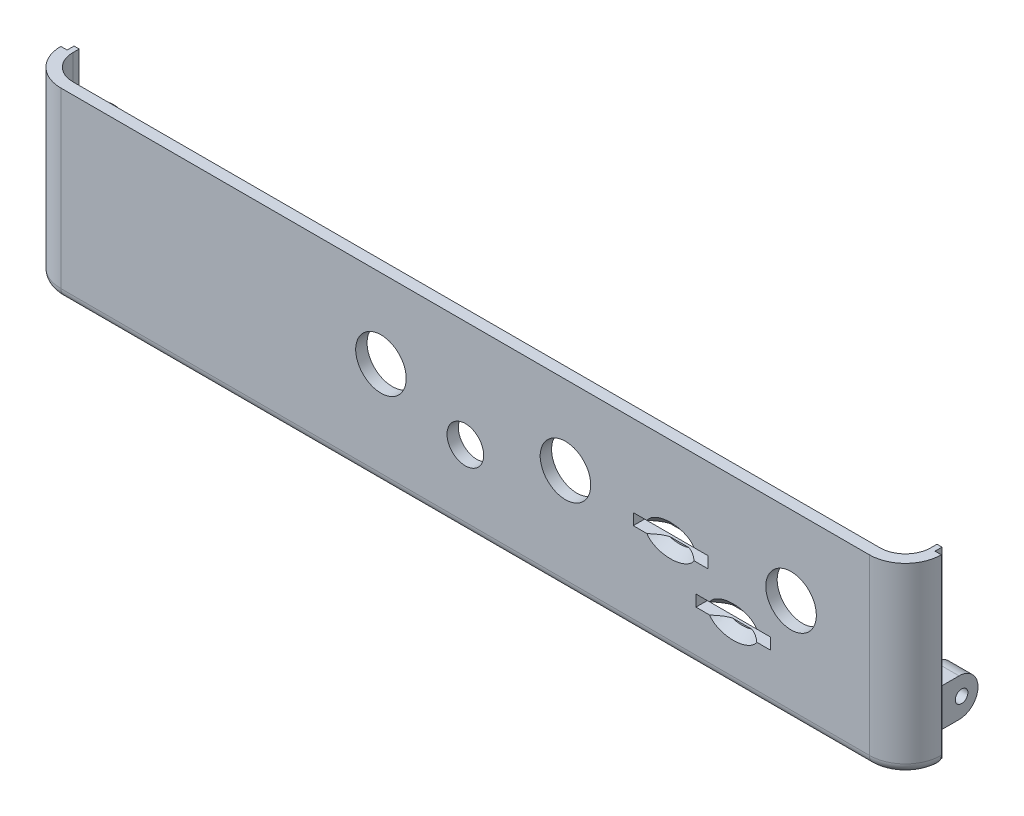
SolidWorks part; units mm, degrees
ref_plane "Спереди" through (0, 0, 0) normal (0, 0, 1) x (1, 0, 0)
ref_plane "Сверху" through (0, 0, 0) normal (0, 1, 0) x (1, 0, 0)
ref_plane "Справа" through (0, 0, 0) normal (1, 0, 0) x (0, 0, -1)
sketch "Эскиз1" plane through (0, 0, 0) normal (0, 0, 1) x (1, 0, 0)
  line L0 (63.5, -15.75) -> (-63.5, -15.75)
  line L1 (63.5, -15.75) -> (67.5, -15.75)
  line L2 (-67.5, -15.75) -> (-63.5, -15.75)
  line L3 (46.9932, -6.75) -> (37.9073, -6.75)
  line L4 (37.9073, -5.75) -> (46.9932, -5.75)
  line L5 (47.9512, -6.625) -> (47.9512, -6.1632)
  line L6 (47.912, -5.875) -> (47.023, -5.875)
  line L7 (47.023, -5.875) -> (47.023, -6.625)
  line L8 (47.023, -6.625) -> (47.9512, -6.625)
  line L9 (36.95, -6.1597) -> (36.95, -6.625)
  line L10 (36.95, -6.625) -> (37.8781, -6.625)
  line L11 (37.8781, -6.625) -> (37.8781, -5.875)
  line L12 (37.8781, -5.875) -> (36.9862, -5.875)
  line L13 (67.5, -13.75) -> (67.5, -15.75)
  line L14 (-67.5, -13.75) -> (-67.5, -15.75)
  line L15 (63.5, -13.75) -> (-63.5, -13.75)
  line L16 (57.5, -7.55) -> (-57.5, -7.55)
  line L17 (-60, -7.55) -> (-60, -9.15)
  line L18 (60, -9.15) -> (60, -7.55)
  line L19 (37.2238, 0.43) -> (27.8238, 0.43)
  line L20 (37.2238, -0.52) -> (27.8238, -0.52)
  line L21 (27.0238, -0.52) -> (27.0238, 0.43)
  line L22 (38.0238, 0.43) -> (38.0238, -0.52)
  line L23 (38.325, 15.75) -> (32.995, 15.75)
  line L24 (43.655, 15.75) -> (38.325, 15.75)
  line L25 (67.5, -13.75) -> (63.5, -13.75)
  line L26 (-63.5, -13.75) -> (-67.5, -13.75)
  line L27 (-26.445, 5.4154) -> (64.8363, 5.4154)
  line L28 (-26.445, 7.0154) -> (64.8363, 7.0154)
  line L29 (63.0185, 5.4154) -> (66.0185, 5.4154)
  line L30 (-24.6275, 7.05) -> (-27.6275, 7.05)
  arc A0 (-11.5687, 1.25) -> (-15.0687, 1.25) centre (-13.3187, 1.25) ccw
  arc A1 (-15.0687, 1.25) -> (-11.5687, 1.25) centre (-13.3187, 1.25) ccw
  arc A2 (53.36, 1.25) -> (49.86, 1.25) centre (51.61, 1.25) ccw
  arc A3 (49.86, 1.25) -> (53.36, 1.25) centre (51.61, 1.25) ccw
  arc A4 (17.6413, 1.25) -> (14.1413, 1.25) centre (15.8913, 1.25) ccw
  arc A5 (14.1413, 1.25) -> (17.6413, 1.25) centre (15.8913, 1.25) ccw
  arc A6 (-1.428, -0.6365) -> (-1.4312, -5.6346) centre (0.0417, -3.1365) ccw
  arc A7 (1.5146, -5.6346) -> (1.5114, -0.6365) centre (0.0417, -3.1365) ccw
  spline S0 degree 3 poles (47.9512, -6.1632) (47.951, -6.1513) (47.9493, -6.1307) (47.9471, -6.1018) knots 0 0 0 0 0.000128 0.000128 0.000128 0.000128 weights 1 1 1 1
  spline S1 degree 3 poles (47.9471, -6.1018) (47.9414, -6.0263) (47.9296, -5.9508) (47.912, -5.875) knots 0 0 0 0 0.000334 0.000334 0.000334 0.000334 weights 1 1 1 1
  spline S2 degree 3 poles (36.953, -6.1018) (36.9512, -6.1281) (36.95, -6.1474) (36.95, -6.1597) knots 0 0 0 0 0.000115 0.000115 0.000115 0.000115 weights 1 1 1 1
  spline S3 degree 3 poles (36.9862, -5.875) (36.9691, -5.9508) (36.958, -6.0264) (36.953, -6.1018) knots 0 0 0 0 0.000335 0.000335 0.000335 0.000335 weights 1 1 1 1
sketch "Эскиз2" plane through (0, 0, 0) normal (0, 0, 1) x (1, 0, 0)
  line L0 (43.655, 15.75) -> (38.325, 15.75) construction
  line L1 (-69.7, 13.75) -> (69.7, 13.75)
  line L2 (-69.7, 13.75) -> (-69.7, -15.35)
  line L3 (-69.7, -15.35) -> (69.7, -15.35)
  line L4 (69.7, 13.75) -> (69.7, -15.35)
  line L5 (63.5, -15.75) -> (-63.5, -15.75) construction
  line L6 (67.5, -13.75) -> (67.5, -15.75) construction
  line L7 (-67.5, -13.75) -> (-67.5, -15.75) construction
  dimension "D1" = 2
  dimension "D2" = 0.4
  dimension "D3" = 2.2
  dimension "D4" = 2.2
extrude "Бобышка-Вытянуть1" add sketch "Эскиз2" along normal blind 1.8
sketch "Эскиз3" plane through (0, 0, 1.8) normal (0, 0, 1) x (1, 0, 0)
  line L0 (37.2238, 0.43) -> (27.8238, 0.43) construction
  line L1 (26.6238, 0.83) -> (38.4238, 0.83)
  line L2 (26.6238, 0.83) -> (26.6238, -0.92)
  line L3 (26.6238, -0.92) -> (38.4238, -0.92)
  line L4 (38.4238, 0.83) -> (38.4238, -0.92)
  line L5 (36.55, -5.35) -> (48.3512, -5.35)
  line L6 (36.55, -5.35) -> (36.55, -7.15)
  line L7 (36.55, -7.15) -> (48.3512, -7.15)
  line L8 (48.3512, -5.35) -> (48.3512, -7.15)
  line L9 (37.2238, -0.52) -> (27.8238, -0.52) construction
  line L10 (27.0238, -0.52) -> (27.0238, 0.43) construction
  line L11 (38.0238, 0.43) -> (38.0238, -0.52) construction
  line L12 (37.9073, -5.75) -> (46.9932, -5.75) construction
  line L13 (46.9932, -6.75) -> (37.9073, -6.75) construction
  line L14 (47.9512, -6.625) -> (47.9512, -6.1632) construction
  line L15 (36.95, -6.1597) -> (36.95, -6.625) construction
  circle A0 centre (0.0417, -3.1365) radius 2.9
  circle A1 centre (-13.3187, 1.25) radius 4
  circle A2 centre (15.8913, 1.25) radius 4
  circle A3 centre (51.61, 1.25) radius 4
  dimension "D1" = 5.8
  dimension "D2" = 8
  dimension "D3" = 0.4
  dimension "D4" = 0.4
  dimension "D5" = 0.4
  dimension "D6" = 0.4
  dimension "D7" = 0.4
  dimension "D8" = 0.4
  dimension "D9" = 0.4
  dimension "D10" = 0.4
extrude "Вырез-Вытянуть1" cut sketch "Эскиз3" against normal blind 1.8
sketch "Эскиз5" plane through (0, 0, 0) normal (0, 0, -1) x (-1, 0, 0)
  line L0 (69.7, -15.35) -> (-69.7, -15.35) construction
  line L1 (69.7, 13.75) -> (67.9, 13.75)
  line L2 (69.7, 13.75) -> (69.7, -15.35)
  line L3 (69.7, -15.35) -> (67.9, -15.35)
  line L4 (67.9, 13.75) -> (67.9, -15.35)
  line L5 (-63.5, -15.75) -> (63.5, -15.75) construction
  line L6 (-69.7, 13.75) -> (-67.9, 13.75)
  line L7 (-69.7, 13.75) -> (-69.7, -15.75)
  line L8 (-69.7, -15.75) -> (-67.9, -15.75)
  line L9 (-67.9, 13.75) -> (-67.9, -15.75)
  dimension "D1" = 1.8
  dimension "D2" = 1.8
extrude "Бобышка-Вытянуть2" add sketch "Эскиз5" along normal blind 5
fillet "Скругление1" radius 4 2 edges at (-67.9, -0.8, 0) (67.9, -0.8, 0)
fillet "Скругление2" radius 5.7 2 edges at (69.7, -0.8, 1.8) (-69.7, -0.8, 1.8)
sketch "Эскиз9" plane through (0, 0, 1.8) normal (0, 0, 1) x (1, 0, 0)
  line L2 (38.4238, 0.83) -> (26.6238, 0.83) construction
  line L3 (26.6238, 0.855) -> (38.4238, 0.855)
  line L4 (26.6238, 0.855) -> (26.6238, -0.945)
  line L5 (26.6238, -0.945) -> (38.4238, -0.945)
  line L6 (38.4238, 0.855) -> (38.4238, -0.945)
  line L9 (38.4238, -0.92) -> (38.4238, 0.83) construction
  dimension "D1" = 1.8
  dimension "D2" = 0.025
  dimension "D3" = 11.8
extrude "Вырез-Вытянуть3" cut sketch "Эскиз9" against normal blind 1.8
sketch "Эскиз11" plane through (0, 0, 1.8) normal (0, 0, 1) x (1, 0, 0)
  line L0 (38.4238, 0.855) -> (26.6238, 0.855) construction
  line L1 (48.3512, -5.35) -> (36.55, -5.35) construction
  line L2 (38.4238, -0.945) -> (38.4238, 0.855) construction
  line L3 (48.3512, -7.15) -> (48.3512, -5.35) construction
  ellipse E0 centre (32.5238, -0.045) end of major axis (28.5238, -0.045) minor radius 2.5
  ellipse E1 centre (42.4512, -6.25) end of major axis (38.4512, -6.25) minor radius 2.5
  dimension "D1" = 0.9
  dimension "D2" = 0.9
  dimension "D3" = 5
  dimension "D4" = 5.9
  dimension "D5" = 5.9
  dimension "D6" = 8
  dimension "D7" = 8
  dimension "D8" = 5
extrude "Вырез-Вытянуть5" cut sketch "Эскиз11" against normal blind 1.4 draft 44
sketch "Эскиз12" plane through (67.9, 0, 0) normal (-1, 0, 0) x (0, 0, 1)
  line L1 (-5, -15.75) -> (0, -15.75)
  line L2 (-5, -15.75) -> (-5, -15.35)
  line L3 (-5, -15.35) -> (0, -15.35)
  line L4 (0, -15.75) -> (0, -15.35)
extrude "Вырез-Вытянуть6" cut sketch "Эскиз12" against normal blind 11.4
sketch "Эскиз13" plane through (0, 0, 0) normal (0, 0, -1) x (-1, 0, 0)
  line L0 (-57.5, -7.55) -> (57.5, -7.55) construction
  line L1 (-60.7, -4.95) -> (-52.7, -4.95)
  line L2 (-60.7, -4.95) -> (-60.7, -6.95)
  line L3 (-60.7, -6.95) -> (-52.7, -6.95)
  line L4 (-52.7, -4.95) -> (-52.7, -6.95)
  line L5 (-60, -9.15) -> (-60, -7.55) construction
  line L6 (60, -7.55) -> (60, -9.15) construction
  line L7 (52.7, -4.95) -> (60.7, -4.95)
  line L8 (52.7, -4.95) -> (52.7, -6.95)
  line L9 (52.7, -6.95) -> (60.7, -6.95)
  line L10 (60.7, -4.95) -> (60.7, -6.95)
  dimension "D1" = 8
  dimension "D2" = 2
  dimension "D3" = 0.6
  dimension "D4" = 0.7
  dimension "D5" = 8
  dimension "D6" = 2
  dimension "D7" = 0.6
  dimension "D8" = 0.7
extrude "Бобышка-Вытянуть3" add sketch "Эскиз13" along normal blind 8
sketch "Эскиз14" plane through (0, -4.95, 0) normal (0, 1, 0) x (1, 0, 0)
  line L0 (60.7, 8) -> (60.7, 0) construction
  line L1 (52.7, 8) -> (60.7, 8) construction
  line L2 (-60.7, 8) -> (-60.7, 0) construction
  line L3 (-60.7, 8) -> (-52.7, 8) construction
  circle A0 centre (-56.7, 4.3) radius 1.6
  circle A1 centre (56.7, 4.3) radius 1.6
  dimension "D1" = 3.2
  dimension "D2" = 4
  dimension "D3" = 3.7
  dimension "D4" = 4
  dimension "D5" = 3.7
extrude "Вырез-Вытянуть7" cut sketch "Эскиз14" against normal blind 10
fillet "Скругление3" radius 3.8 8 edges at (60.7, -5.95, -8) (52.7, -5.95, -8) (-60.7, -5.95, 0) (52.7, -5.95, 0) (60.7, -5.95, 0) (-52.7, -5.95, 0) (-60.7, -5.95, -8) (-52.7, -5.95, -8)
sketch "Эскиз18" plane through (0, -15.35, 0) normal (0, -1, 0) x (1, 0, 0)
  line L0 (67.9, -4) -> (67.9, -5) construction
  line L1 (67.9, -4) -> (67.9, -5)
  line L2 (-63.9, 0) -> (63.9, 0) construction
  line L3 (-63.9, 0) -> (63.9, 0)
  line L4 (-67.9, -5) -> (-67.9, -4) construction
  line L5 (-67.9, -5) -> (-67.9, -4)
  arc A0 (67.9, -4) -> (63.9, 0) centre (63.9, -4) ccw construction
  arc A1 (67.9, -4) -> (63.9, 0) centre (63.9, -4) ccw
  arc A2 (-63.9, 0) -> (-67.9, -4) centre (-63.9, -4) ccw construction
  arc A3 (-63.9, 0) -> (-67.9, -4) centre (-63.9, -4) ccw
extrude "Вытянуть-Тонкостенный1" add sketch "Эскиз18" against normal blind 3.8 and the other way blind 1 thin
sketch "Эскиз19" plane through (0, -16.35, 0) normal (0, -1, 0) x (1, 0, 0)
  line L8 (66.9, -4) -> (66.9, -5)
  line L9 (66.9, -5) -> (67.9, -5)
  line L10 (67.9, -5) -> (67.9, -4)
  line L11 (63.9, 0) -> (-63.9, 0)
  line L12 (-67.9, -4) -> (-67.9, -5)
  line L13 (-67.9, -5) -> (-66.9, -5)
  line L14 (-66.9, -5) -> (-66.9, -4)
  line L15 (-63.9, -1) -> (63.9, -1)
  line L16 (66.9, -4) -> (66.9, -5)
  line L17 (66.9, -5) -> (67.9, -5)
  line L18 (67.9, -5) -> (67.9, -4)
  line L19 (63.9, 0) -> (-63.9, 0)
  line L20 (-67.9, -4) -> (-67.9, -5)
  line L21 (-67.9, -5) -> (-66.9, -5)
  line L22 (-66.9, -5) -> (-66.9, -4)
  line L23 (-63.9, -1) -> (63.9, -1)
  arc A4 (67.9, -4) -> (63.9, 0) centre (63.9, -4) ccw
  arc A5 (-63.9, 0) -> (-67.9, -4) centre (-63.9, -4) ccw
  arc A6 (-63.9, -1) -> (-66.9, -4) centre (-63.9, -4) ccw
  arc A7 (66.9, -4) -> (63.9, -1) centre (63.9, -4) ccw
  arc A8 (67.9, -4) -> (63.9, 0) centre (63.9, -4) ccw
  arc A9 (-63.9, 0) -> (-67.9, -4) centre (-63.9, -4) ccw
  arc A10 (-63.9, -1) -> (-66.9, -4) centre (-63.9, -4) ccw
  arc A11 (66.9, -4) -> (63.9, -1) centre (63.9, -4) ccw
  dimension "D1" = 0
extrude "Вырез-Вытянуть8" cut sketch "Эскиз19" against normal blind 3.1
sketch "Эскиз20" plane through (0, -11.55, 0) normal (0, 1, 0) x (1, 0, 0)
  line L0 (67.9, 5) -> (67.9, 4) construction
  line L1 (-63.9, 0) -> (63.9, 0) construction
  line L2 (-67.9, 5) -> (-67.9, 4) construction
  circle A0 centre (-64.4, 3.5) radius 3.5
  circle A1 centre (64.4, 3.5) radius 3.5
  circle A2 centre (-26, 3.5) radius 3.55
  dimension "D1" = 7
  dimension "D2" = 7
  dimension "D3" = 3.5
  dimension "D4" = 3.5
  dimension "D5" = 3.5
  dimension "D6" = 3.5
  dimension "D7" = 7.1
  dimension "D8" = 90.4
extrude "Бобышка-Вытянуть6" add sketch "Эскиз20" along normal blind 16.7 and the other way blind 1.7
sketch "Эскиз23" plane through (0, 5.15, 0) normal (0, 1, 0) x (1, 0, 0)
  circle A0 centre (-64.4, 3.5) radius 1
  circle A1 centre (-26, 3.5) radius 1
  circle A2 centre (64.4, 3.5) radius 1
  dimension "D1" = 2
extrude "Вырез-Вытянуть9" cut sketch "Эскиз23" against normal blind 20
sketch "Эскиз24" plane through (0, 5.15, 0) normal (0, 1, 0) x (1, 0, 0)
  line L2 (-67.9, 5) -> (-67.2764, 5)
  line L3 (-67.9, 5) -> (-67.9, 2.059)
  line L4 (-67.9, 2.059) -> (-67.2764, 2.059)
  line L5 (-67.2764, 5) -> (-67.2764, 2.059)
  line L6 (-60.9, 3.5) -> (-62.4575, 3.5)
  line L7 (-60.9, 3.5) -> (-60.9, -0.9822)
  line L8 (-60.9, -0.9822) -> (-62.4575, -0.9822)
  line L9 (-62.4575, 3.5) -> (-62.4575, -0.9822)
  line L10 (-64.1584, 0.0084) -> (-62.4575, 0.0084)
  line L11 (-64.1584, 0.0084) -> (-64.1584, 2.059)
  line L12 (-64.1584, 2.059) -> (-62.4575, 2.059)
  line L13 (-62.4575, 0.0084) -> (-62.4575, 2.059)
  line L14 (-29.55, 3.5) -> (-28.2836, 3.5)
  line L15 (-29.55, 3.5) -> (-29.55, -0.9822)
  line L16 (-29.55, -0.9822) -> (-28.2836, -0.9822)
  line L17 (-28.2836, 3.5) -> (-28.2836, -0.9822)
  line L18 (-22.45, 3.5) -> (-24.2804, 3.5)
  line L19 (-22.45, 3.5) -> (-22.45, -0.9822)
  line L20 (-22.45, -0.9822) -> (-24.2804, -0.9822)
  line L21 (-24.2804, 3.5) -> (-24.2804, -0.9822)
  line L22 (67.8916, 3.7416) -> (66.8457, 3.7416)
  line L23 (67.8916, 3.7416) -> (67.8916, 5)
  line L24 (67.8916, 5) -> (66.8457, 5)
  line L25 (66.8457, 3.7416) -> (66.8457, 5)
  line L26 (60.9, 3.5) -> (62.7277, 3.5)
  line L27 (60.9, 3.5) -> (60.9, -0.9822)
  line L28 (60.9, -0.9822) -> (62.7277, -0.9822)
  line L29 (62.7277, 3.5) -> (62.7277, -0.9822)
  line L30 (64.1584, 0.0084) -> (62.7277, 0.0084)
  line L31 (64.1584, 0.0084) -> (64.1584, 1.4963)
  line L32 (64.1584, 1.4963) -> (62.7277, 1.4963)
  line L33 (62.7277, 0.0084) -> (62.7277, 1.4963)
  line L34 (-28.2836, 1.2589) -> (-24.2804, 1.2589)
  line L35 (-28.2836, 1.2589) -> (-28.2836, -0.9822)
  line L36 (-28.2836, -0.9822) -> (-24.2804, -0.9822)
  line L37 (-24.2804, 1.2589) -> (-24.2804, -0.9822)
  arc A0 (-64.1584, 0.0084) -> (-67.8916, 3.7416) centre (-64.4, 3.5) ccw construction
  arc A1 (-25.4063, 0) -> (-26.5937, 0) centre (-26, 3.5) ccw construction
  arc A2 (67.8916, 3.7416) -> (64.1584, 0.0084) centre (64.4, 3.5) ccw construction
  arc M2 (-67.8916, 3.7416) -> (-64.1584, 0.0084) centre (-63.9, 4) ccw
  arc M3 (-64.1584, 0.0084) -> (-67.8916, 3.7416) centre (-64.4, 3.5) ccw
extrude "Бобышка-Вытянуть9" add sketch "Эскиз24" against normal blind 18.4 contours L25 L22 L23 L24 | L31 L32 L29 L30 | L29 L26 L27 L28 | L18 L21 L20 L19 | L17 L14 L15 L16 | L9 L8 L7 M3 | L12 L11 L9 M3 | L5 L2 L4 M3 M2 | L35 L34 L37 L36
sketch "Эскиз25" plane through (0, 5.15, 0) normal (0, 1, 0) x (1, 0, 0)
  line L6 (-64.1584, 0.0084) -> (-62.4575, 0.0084)
  line L7 (-62.4575, 0.0084) -> (-62.4575, 0)
  line L8 (-62.4575, 0) -> (-60.9, 0)
  line L9 (-60.9, 0) -> (-60.9, 3.5)
  line L10 (-67.5623, 5) -> (-67.9, 5)
  line L11 (-67.9, 5) -> (-67.9, 4)
  line L12 (-64.1584, 0.0084) -> (-62.4575, 0.0084)
  line L13 (-62.4575, 0.0084) -> (-62.4575, 0)
  line L14 (-62.4575, 0) -> (-60.9, 0)
  line L15 (-60.9, 0) -> (-60.9, 3.5)
  line L16 (-67.5623, 5) -> (-67.9, 5)
  line L17 (-67.9, 5) -> (-67.9, 4)
  circle A0 centre (-64.4, 3.5) radius 1 construction
  circle A1 centre (-64.4, 3.5) radius 1
  arc A2 (-67.9, 4) -> (-64.1584, 0.0084) centre (-63.9, 4) ccw
  arc A3 (-60.9, 3.5) -> (-67.5623, 5) centre (-64.4, 3.5) ccw
  arc A4 (-67.9, 4) -> (-64.1584, 0.0084) centre (-63.9, 4) ccw
  arc A5 (-60.9, 3.5) -> (-67.5623, 5) centre (-64.4, 3.5) ccw
  dimension "D1" = 0
extrude "Бобышка-Вытянуть10" add sketch "Эскиз25" along normal blind 1.7
sketch "Эскиз26" plane through (0, -13.25, 0) normal (0, -1, 0) x (1, 0, 0)
  line L1 (-63.9, 0) -> (63.9, 0) construction
  line L2 (-29.55, 0) -> (-22.45, 0)
  line L3 (-29.55, 0) -> (-29.55, -7.05)
  line L4 (-29.55, -7.05) -> (-22.45, -7.05)
  line L5 (-22.45, 0) -> (-22.45, -7.05)
extrude "Вырез-Вытянуть10" cut sketch "Эскиз26" against normal blind 8
sketch "Эскиз27" plane through (-29.55, 0, 0) normal (1, 0, 0) x (0, 0, -1)
  line L4 (1, -11.55) -> (0, -11.55)
  line L5 (0, -11.55) -> (0, -13.25)
  line L6 (0, -13.25) -> (1, -13.25)
  line L7 (1, -13.25) -> (1, -11.55)
  line L8 (1, -11.55) -> (0, -11.55)
  line L9 (0, -11.55) -> (0, -13.25)
  line L10 (0, -13.25) -> (1, -13.25)
  line L11 (1, -13.25) -> (1, -11.55)
  dimension "D1" = 0
extrude "Бобышка-Вытянуть11" add sketch "Эскиз27" along normal blind 8
chamfer "Фаска2" distance 1 angle 45 3 edges at (60.9, -11.55, -0.5) (0, -11.55, 0) (-60.9, -11.55, -0.5)
sketch "Эскиз29" plane through (69.7, 0, 0) normal (1, 0, 0) x (0, 0, -1)
  line L1 (7.05, 5.15) -> (6.45, 5.15)
  line L2 (7.05, 5.15) -> (7.05, -1.25)
  line L3 (7.05, -1.25) -> (6.45, -1.25)
  line L4 (6.45, 5.15) -> (6.45, -1.25)
  dimension "D1" = 6.4
  dimension "D2" = 0.6
extrude "Вырез-Вытянуть11" cut sketch "Эскиз29" against normal blind 8
chamfer "Фаска3" distance 0.5 angle 45 1 edges at (64.4, -1.25, -7)
sketch "Эскиз30" plane through (69.7, 0, 0) normal (1, 0, 0) x (0, 0, -1)
  line L4 (3.9, 13.75) -> (3.9, -15.35)
  line L5 (3.9, -15.35) -> (5, -15.35)
  line L6 (5, -15.35) -> (5, 13.75)
  line L7 (5, 13.75) -> (3.9, 13.75)
  line L8 (3.9, 13.75) -> (3.9, -15.35)
  line L9 (3.9, -15.35) -> (5, -15.35)
  line L10 (5, -15.35) -> (5, 13.75)
  line L11 (5, 13.75) -> (3.9, 13.75)
  dimension "D1" = 0
extrude "Вырез-Вытянуть12" cut sketch "Эскиз30" against normal blind 1
sketch "Эскиз31" plane through (-69.7, 0, 0) normal (-1, 0, 0) x (0, 0, 1)
  line L4 (-5, -15.35) -> (-3.9, -15.35)
  line L5 (-3.9, -15.35) -> (-3.9, 13.75)
  line L6 (-3.9, 13.75) -> (-5, 13.75)
  line L7 (-5, 13.75) -> (-5, -15.35)
  line L8 (-5, -15.35) -> (-3.9, -15.35)
  line L9 (-3.9, -15.35) -> (-3.9, 13.75)
  line L10 (-3.9, 13.75) -> (-5, 13.75)
  line L11 (-5, 13.75) -> (-5, -15.35)
  dimension "D1" = 0
extrude "Вырез-Вытянуть13" cut sketch "Эскиз31" against normal blind 1
sketch "Эскиз33" plane through (-67.9, 0, 0) normal (1, 0, 0) x (0, 0, -1)
  line L1 (5, -13.25) -> (12.7, -13.25)
  line L2 (5, -13.25) -> (5, -7.25)
  line L3 (5, -7.25) -> (12.7, -7.25)
  line L4 (12.7, -13.25) -> (12.7, -7.25)
  dimension "D1" = 7.7
  dimension "D2" = 6
extrude "Бобышка-Вытянуть12" add sketch "Эскиз33" along normal blind 5
sketch "Эскиз34" plane through (0, -7.25, 0) normal (0, 1, 0) x (1, 0, 0)
  line L0 (-67.9, 12.7) -> (-66.7, 12.7)
  line L1 (-62.9, 12.7) -> (-67.9, 12.7) construction
  line L2 (-66.7, 12.7) -> (-66.7, 6.1382)
  line L3 (-67.9, 12.7) -> (-67.9, 5) construction
  line L4 (-67.9, 12.7) -> (-67.9, 5)
  line L5 (-67.5623, 5) -> (-67.9, 5) construction
  line L6 (-67.5623, 5) -> (-67.9, 5)
  arc A0 (-62.9, 6.6623) -> (-67.5623, 5) centre (-64.4, 3.5) ccw construction
  arc A1 (-60.9, 3.5) -> (-67.5623, 5) centre (-64.4, 3.5) ccw construction
  arc A2 (-60.9, 3.5) -> (-67.5623, 5) centre (-64.4, 3.5) ccw
  arc M2 (-67.5623, 5) -> (-62.9, 6.6623) centre (-64.4, 3.5) cw
  line M4 (-62.9, 12.7) -> (-67.9, 12.7)
  line M5 (-67.9, 12.7) -> (-67.9, 5)
  line M6 (-67.9, 5) -> (-67.5623, 5)
  dimension "D1" = 1.2
extrude "Вырез-Вытянуть14" cut sketch "Эскиз34" against normal through all contours L2 M4 M5 M6 M2
sketch "Эскиз37" plane through (0, 0, -5) normal (0, 0, -1) x (-1, 0, 0)
  line L0 (-68.7, -15.35) -> (-68.7, 13.75) construction
  line L1 (-68.7, -15.35) -> (-68.7, 13.75)
  line L2 (-67.9, 13.75) -> (-68.7, 13.75) construction
  line L3 (-67.9, 13.75) -> (-68.7, 13.75)
  line L4 (-68.7, -15.35) -> (-67.9, -15.35) construction
  line L5 (-68.7, -15.35) -> (-67.9, -15.35)
  line L6 (-67.9, -13.25) -> (-67.9, -15.35) construction
  line L7 (-67.9, -13.25) -> (-67.9, -15.35)
  line L8 (-67.5623, -13.25) -> (-67.9, -13.25) construction
  line L9 (-67.5623, -13.25) -> (-67.9, -13.25)
  line L10 (-67.5623, 5.15) -> (-67.5623, -13.25) construction
  line L11 (-67.5623, 5.15) -> (-67.5623, -13.25)
  line L12 (-67.8916, 5.15) -> (-67.5623, 5.15) construction
  line L13 (-67.8916, 5.15) -> (-67.5623, 5.15)
  line L14 (-67.9, 13.75) -> (-67.8916, 5.15)
extrude "Бобышка-Вытянуть17" add sketch "Эскиз37" against normal blind 0.8
sketch "Эскиз38" plane through (67.9, 0, 0) normal (-1, 0, 0) x (0, 0, 1)
  line L1 (-5, -13.25) -> (-12.7, -13.25)
  line L2 (-5, -13.25) -> (-5, -7.25)
  line L3 (-5, -7.25) -> (-12.7, -7.25)
  line L4 (-12.7, -13.25) -> (-12.7, -7.25)
  dimension "D1" = 7.7
  dimension "D2" = 6
extrude "Бобышка-Вытянуть18" add sketch "Эскиз38" along normal blind 5
sketch "Эскиз39" plane through (0, -7.25, 0) normal (0, 1, 0) x (1, 0, 0)
  line L0 (67.9, 5) -> (67.9, 12.7) construction
  line L1 (67.9, 5) -> (67.9, 12.7)
  line L2 (67.5623, 5) -> (67.9, 5) construction
  line L3 (67.5623, 5) -> (67.9, 5)
  line L5 (66.7, 12.7) -> (67.9, 12.7)
  line L6 (66.7, 12.7) -> (66.7, 6.1382)
  arc A0 (67.5623, 5) -> (62.9, 6.6623) centre (64.4, 3.5) ccw construction
  arc A1 (67.5623, 5) -> (62.9, 6.6623) centre (64.4, 3.5) ccw
  arc M3 (62.9, 6.6623) -> (67.5623, 5) centre (64.4, 3.5) cw
  line M4 (67.5623, 5) -> (67.9, 5)
  line M5 (67.9, 5) -> (67.9, 12.7)
  line M6 (67.9, 12.7) -> (62.9, 12.7)
  dimension "D1" = 1.2
extrude "Вырез-Вытянуть15" cut sketch "Эскиз39" against normal through all contours L6 M6 M3 M4 M5
fillet "Скругление5" radius 3 4 edges at (64.8, -13.25, -12.7) (64.8, -7.25, -12.7) (-64.8, -7.25, -12.7) (-64.8, -13.25, -12.7)
sketch "Эскиз40" plane through (-66.7, 0, 0) normal (-1, 0, 0) x (0, 0, 1)
  line L0 (-6.1382, -13.25) -> (-9.7, -13.25) construction
  circle A0 centre (-10.1, -10.25) radius 1
  dimension "D1" = 2
  dimension "D2" = 3
  dimension "D3" = 2.6
extrude "Вырез-Вытянуть16" cut sketch "Эскиз40" against normal through all
fillet "Скругление6" radius 1.6 3 edges at (-68.0305, -15.35, 0.1305) (68.0305, -15.35, 0.1305) (0, -15.35, 1.8)
equation "\"52.8.00мм\"=5"
